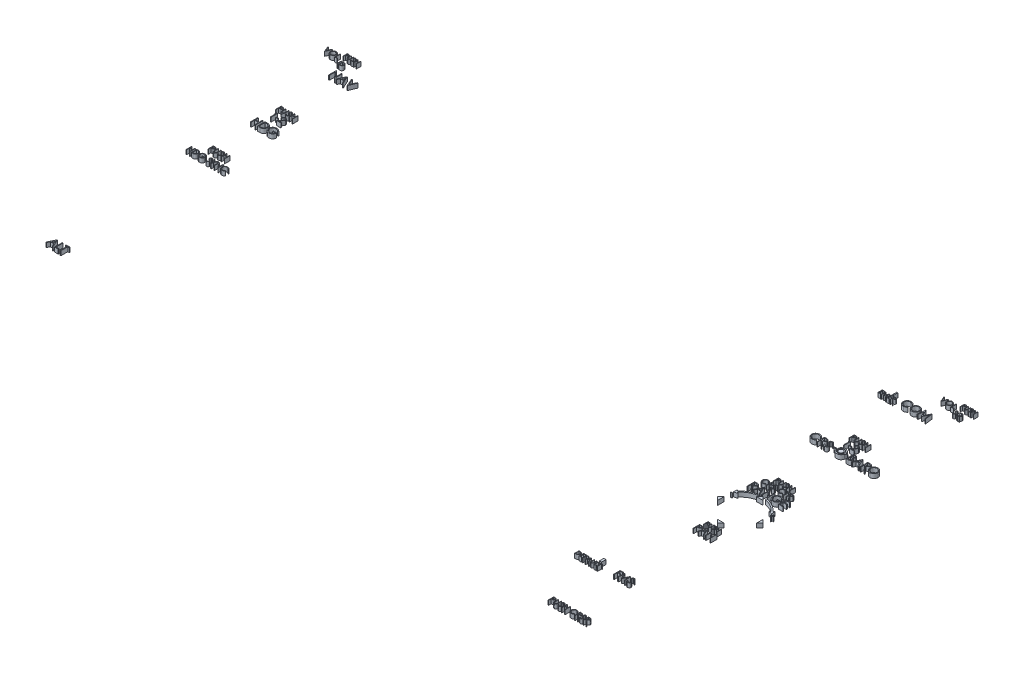
SolidWorks part; units mm, degrees
ref_plane "Front Plane" through (0, 0, 0) normal (0, 0, 1) x (1, 0, 0)
ref_plane "Top Plane" through (0, 0, 0) normal (0, 1, 0) x (1, 0, 0)
ref_plane "Right Plane" through (0, 0, 0) normal (1, 0, 0) x (0, 0, -1)
sketch "Sketch2" plane through (0, 0, 0) normal (0, 1, 0) x (1, 0, 0)
  line L0 (99.8654, 74.3211) -> (102.4584, 74.3211) construction
  line L1 (102.4584, 74.3211) -> (102.9584, 74.3211)
  line L2 (102.4584, 74.3211) -> (102.4584, 72.4004)
  line L3 (102.4584, 72.4004) -> (102.9584, 72.4004)
  line L4 (102.9584, 74.3211) -> (102.9584, 72.4004)
  line L5 (113.1779, 38.0362) -> (109.3395, 36.6391) construction
  line L6 (113.1779, 38.0362) -> (109.3395, 39.4333) construction
  line L7 (106.8165, 38.0362) -> (119.2503, 38.0362) construction
  line L8 (111.2986, 38.7202) -> (111.7684, 38.5492)
  line L9 (111.2986, 37.3522) -> (111.7684, 37.5232)
  line L10 (111.8654, 0.5211) -> (114.8654, 0.5211)
  line L11 (112.196, 37.8352) -> (109.9947, 37.8352)
  line L12 (114.8654, 0.5211) -> (113.3654, 2.0211)
  line L13 (112.196, 38.2372) -> (109.9947, 38.2372)
  line L14 (109.9947, 37.8352) -> (109.9947, 38.2372)
  line L15 (115.1678, 38.2372) -> (116.1678, 38.2372)
  line L16 (113.3654, 2.0211) -> (111.8654, 0.5211)
  line L17 (115.1678, 37.8352) -> (116.1678, 37.8352)
  line L18 (116.1678, 38.2372) -> (116.1678, 37.8352)
  line L19 (113.3654, -8.4789) -> (113.3654, 4.1742) construction
  line L20 (122.3654, -6.9789) -> (122.3654, -9.9789)
  line L21 (122.3654, -9.9789) -> (123.8654, -8.4789)
  line L22 (123.8654, -8.4789) -> (122.3654, -6.9789)
  line L23 (114.8654, -17.4789) -> (111.8654, -17.4789)
  line L24 (111.8654, -17.4789) -> (113.3654, -18.9789)
  line L25 (113.3654, -18.9789) -> (114.8654, -17.4789)
  line L26 (104.3654, -9.9789) -> (104.3654, -6.9789)
  line L27 (104.3654, -6.9789) -> (102.8654, -8.4789)
  line L28 (102.8654, -8.4789) -> (104.3654, -9.9789)
  line L29 (113.3654, -8.4789) -> (100.7145, 2.1365) construction
  line L30 (113.3654, -8.4789) -> (111.8654, 0.5211) construction
  line L31 (111.6228, 1.9769) -> (111.7214, 1.3851)
  line L32 (105.2454, -1.6653) -> (104.7414, -1.2425)
  line L33 (104.7414, -1.2425) -> (104.5753, -2.9306)
  line L34 (104.5753, -2.9306) -> (106.2089, -2.4738)
  line L35 (106.2089, -2.4738) -> (105.705, -2.051)
  line L36 (115.1081, 1.9769) -> (115.0094, 1.3851)
  line L37 (120.5219, -2.4738) -> (121.0259, -2.051)
  line L38 (122.1556, -2.9306) -> (120.5219, -2.4738)
  line L39 (121.9894, -1.2425) -> (122.1556, -2.9306)
  line L40 (121.4855, -1.6653) -> (121.9894, -1.2425)
  line L41 (96.6654, -59.1789) -> (106.8654, -59.1789) construction
  line L42 (101.2654, -59.1789) -> (102.2654, -59.1789)
  line L43 (101.2654, -59.1789) -> (101.2654, -61.1789)
  line L44 (101.2654, -61.1789) -> (102.2654, -61.1789)
  line L45 (102.2654, -59.1789) -> (102.2654, -61.1789)
  arc A0 (115.1678, 38.2372) -> (111.2986, 38.7202) centre (113.1779, 38.0362) ccw
  arc A1 (111.7684, 37.5232) -> (111.7684, 38.5492) centre (113.1779, 38.0362) ccw
  arc A2 (112.196, 38.2372) -> (112.196, 37.8352) centre (113.1779, 38.0362) cw
  arc A3 (115.1678, 37.8352) -> (111.2986, 37.3522) centre (113.1779, 38.0362) cw
  circle A4 centre (113.3654, -8.4789) radius 8 construction
  arc A5 (111.7214, 1.3851) -> (105.705, -2.051) centre (113.3654, -8.4789) ccw
  arc A6 (111.6228, 1.9769) -> (105.2454, -1.6653) centre (113.3654, -8.4789) ccw
  arc A7 (115.1081, 1.9769) -> (121.4855, -1.6653) centre (113.3654, -8.4789) cw
  arc A8 (115.0094, 1.3851) -> (121.0259, -2.051) centre (113.3654, -8.4789) cw
  text T0 "VOL" font "Century Gothic" height 2.5
  text T1 "PUSH\r\n  ID" font "Century Gothic" height 2
  text T2 "PUSH" font "Century Gothic" height 2.5
  text T3 "1-2" font "Century Gothic" height 3
  text T4 "HDG"
  text T5 "NAV"
  text T6 "     PUSH\r\nHDG SYNC" font "Century Gothic" height 2.5
  text T7 "ALT"
  text T8 "VOL" font "Century Gothic" height 2.5
  text T9 "PUSH\r\n SQ" font "Century Gothic" height 2
  text T10 "COM"
  text T11 "EMER" font "Century Gothic" height 2
  text T12 "PUSH" font "Century Gothic" height 2.5
  text T13 "1-2" font "Century Gothic" height 3
  text T14 "CRS"
  text T15 "BARO"
  text T16 "PUSH" font "Century Gothic" height 2.5
  text T17 "CRS CTR" font "Century Gothic" height 2.5
  text T18 "RANGE"
  text T19 "-" font "Century Gothic" height 2
  text T20 "+" font "Century Gothic" height 2
  text T21 "PUSH" font "Century Gothic" height 2
  text T22 "PAN" font "Century Gothic" height 3
  text T23 "DEFAULT" font "Century Gothic" height 2
  text T24 "FMS" font "Century Gothic" height 3
  text T25 "PUSH CRSR" font "Century Gothic" height 2.5
  point P61 (113.3654, -8.4789)
  point P88 (101.7654, -59.1789)
  point P89 (101.7654, -59.1789)
  dimension "D1" = 3
  dimension "D2" = 20
  dimension "D4" = 1.5
  dimension "D5" = 9
  dimension "D8" = 10
  dimension "D9" = 10.6
  dimension "D3" = 20
  dimension "D6" = 4
  dimension "D7" = 50
  dimension "D10" = 1.4
  dimension "D11" = 1
  dimension "D12" = 2
extrude "Boss-Extrude1" add sketch "Sketch2" along normal blind 2
